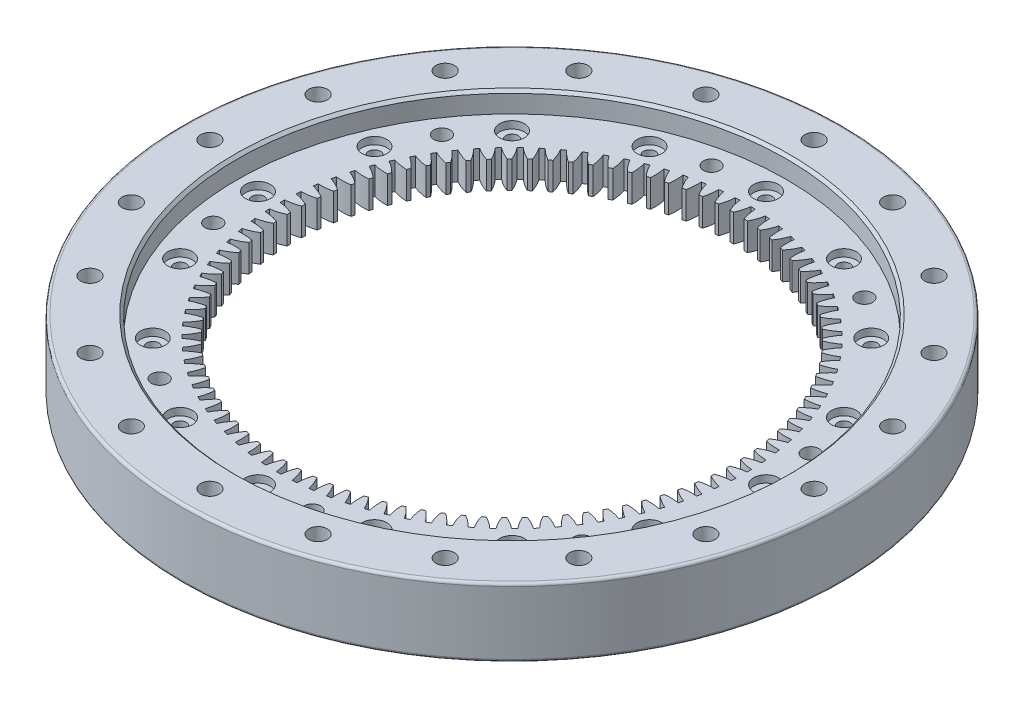
SolidWorks part; units mm, degrees
ref_plane "Front Plane" through (0, 0, 0) normal (0, 0, 1) x (1, 0, 0)
ref_plane "Top Plane" through (0, 0, 0) normal (0, 1, 0) x (1, 0, 0)
ref_plane "Right Plane" through (0, 0, 0) normal (1, 0, 0) x (0, 0, -1)
sketch "Sketch2" plane through (0, 0, 0) normal (1, 0, 0) x (0, 0, -1)
  line L0 (0, 0) -> (0, 63.1953) construction
  line L1 (170, 0) -> (240, 0)
  line L2 (240, 0) -> (240, 25)
  line L3 (240, 25) -> (200, 25)
  line L4 (200, 25) -> (200, 10)
  line L5 (200, 10) -> (170, 10)
  line L6 (170, 10) -> (170, 0)
  dimension "D1" = 240
  dimension "D2" = 170
  dimension "D3" = 200
  dimension "D4" = 25
  dimension "D5" = 10
revolve "Revolve1" add sketch "Sketch2" angle 360 about L0
mirror "Mirror2" about plane through (0, 0, 0) normal (0, 1, 0) of "Revolve1"
ref_axis "Axis1" through (0, 25, 0) along (0, -1, 0)
sketch "Sketch4" plane through (0, 10, 0) normal (0, 1, 0) x (1, 0, 0)
  line L0 (0, 200) -> (0, 170) construction
  circle A0 centre (0, 0) radius 200 construction
  circle A1 centre (0, 0) radius 200 construction
  circle A2 centre (0, 0) radius 170 construction
  point P9 (0, 185)
hole_wizard "CBORE for M8 Hex Head Bolt1" positions "3DSketch1" profile "Sketch5" counterbore size "M8" standard "ISO" end condition through all
sketch3d "3DSketch1"
  point P0 (0, 10, -185)
sketch "Sketch5" plane through (0, 10, -185) normal (1, 0, 0) x (0, 0, 1)
  line L0 (0, 0) -> (0, 35)
  line L1 (0, 35) -> (4.5, 35)
  line L3 (4.5, 35) -> (4.5, 5.3)
  line L4 (4.5, 5.3) -> (9.0055, 5.3)
  line L5 (9.0055, 5.3) -> (9.0055, 0)
  line L7 (9.0055, 0) -> (0, 0)
  line L11 (0, -6.35) -> (0, 107.95) construction
  dimension "Thru Hole Dia." = 9
  dimension "Thru Hole Depth" = 35
  dimension "C'Bore Dia." = 18.011
  dimension "C'Bore Depth" = 5.3
pattern_circular "CirPattern1" count 16 over 360 about axis through (0, 25, 0) along (0, -1, 0) of "CBORE for M8 Hex Head Bolt1"
sketch "Sketch6" plane through (0, -25, 0) normal (0, -1, 0) x (1, 0, 0)
  line L0 (0, 240) -> (0, 200) construction
  circle A0 centre (0, 0) radius 240 construction
  circle A1 centre (0, 0) radius 200 construction
  point P7 (0, 220)
hole_wizard "CBORE for M12 Hex Head Bolt1" positions "3DSketch2" profile "Sketch7" counterbore size "M12" standard "ISO" end condition through all
sketch3d "3DSketch2"
  point P0 (0, -25, 220)
sketch "Sketch7" plane through (0, -25, 220) normal (1, 0, 0) x (0, 0, -1)
  line L0 (0, 0) -> (0, 50)
  line L1 (0, 50) -> (6.75, 50)
  line L3 (6.75, 50) -> (6.75, 7.5)
  line L4 (6.75, 7.5) -> (11.8925, 7.5)
  line L5 (11.8925, 7.5) -> (11.8925, 0)
  line L7 (11.8925, 0) -> (0, 0)
  line L11 (0, -6.35) -> (0, 107.95) construction
  dimension "Thru Hole Dia." = 13.5
  dimension "Thru Hole Depth" = 50
  dimension "C'Bore Dia." = 23.785
  dimension "C'Bore Depth" = 7.5
pattern_circular "CirPattern2" count 20 over 360 about axis through (0, 25, 0) along (0, -1, 0) of "CBORE for M12 Hex Head Bolt1"
sketch "Sketch8" plane through (0, 10, 0) normal (0, 1, 0) x (1, 0, 0)
  line L0 (0, 0) -> (0, 170) construction
  circle A0 centre (0, 0) radius 170 construction
  circle A1 centre (0, 0) radius 170
  circle A3 centre (0, 0) radius 160
  arc A4 (-4, 169.9529) -> (-1.25, 159.9951) centre (30.7427, 174.189) ccw
  arc A5 (4, 169.9529) -> (1.25, 159.9951) centre (-30.7427, 174.189) cw
  circle M32 centre (0, 0) radius 170
  dimension "D4" = 35
  dimension "D2" = 2.5
  dimension "D3" = 8
  dimension "D1" = 10
extrude "Boss-Extrude1" add sketch "Sketch8" against normal up to surface (20 mm away) contours L0 A3 A5 A1 | A3 L0 A4 M32 region at (-1.5555, 10, -165.7789) region at (1.5555, 10, -165.7789) up to face at (133.9967, -10, -133.9967)
pattern_circular "CirPattern3" count 95 over 360 about axis through (0, 25, 0) along (0, -1, 0) of "Boss-Extrude1"
sketch "Sketch11" plane through (0, 10, 0) normal (0, 1, 0) x (1, 0, 0)
  line L0 (0, 185) -> (0, 0) construction
  line L1 (0, 0) -> (-70.7964, 170.9177) construction
  line L2 (0, 0) -> (-36.0917, 181.4453) construction
  circle A0 centre (-36.0917, 181.4453) radius 6
  circle A1 centre (0, 0) radius 185 construction
  dimension "D2" = 12
  dimension "D1" = 11.25
extrude "Cut-Extrude1" cut sketch "Sketch11" against normal through all
pattern_circular "CirPattern4" count 8 over 360 about axis through (0, 25, 0) along (0, -1, 0) of "Cut-Extrude1"
chamfer "Chamfer1" distance 2 angle 45 2 edges at (0, 25, -200) (0, -25, -200)
fillet "Fillet1" radius 2 2 edges at (0, -25, -240) (0, 25, -240)
